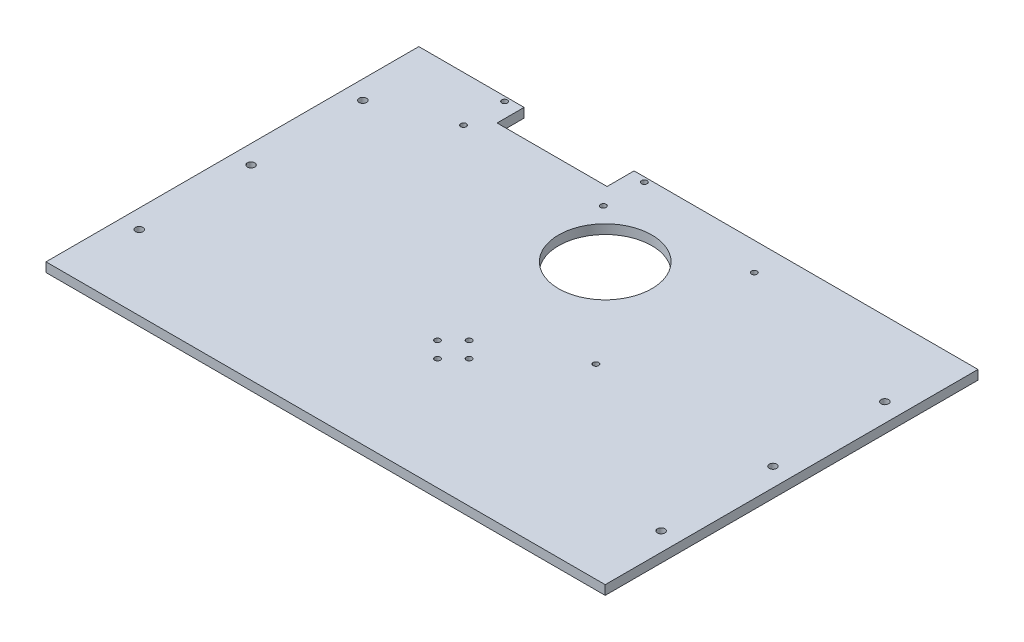
SolidWorks part; units mm, degrees
ref_plane "前视基准面" through (0, 0, 0) normal (0, 0, 1) x (1, 0, 0)
ref_plane "上视基准面" through (0, 0, 0) normal (0, 1, 0) x (1, 0, 0)
ref_plane "右视基准面" through (0, 0, 0) normal (1, 0, 0) x (0, 0, -1)
sketch "Sketch1" plane through (0, 0, 0) normal (0, 1, 0) x (1, 0, 0)
  line L1 (-150, 100) -> (150, 100)
  line L2 (-150, 100) -> (-150, -100)
  line L3 (-150, -100) -> (150, -100)
  line L4 (150, 100) -> (150, -100)
  line L5 (-150, 100) -> (150, -100) construction
  line L6 (-150, -100) -> (150, 100) construction
  point P0 (0, 0)
  dimension "D1" = 200
  dimension "D2" = 300
extrude "Boss-Extrude1" add sketch "Sketch1" along normal blind 5
sketch "Sketch2" plane through (0, 5, 0) normal (0, 1, 0) x (1, 0, 0)
  line L0 (-140, 100) -> (-140, -100) construction
  line L1 (150, 100) -> (-150, 100) construction
  line L2 (-150, -100) -> (150, -100) construction
  line L3 (-150, -90) -> (150, -90) construction
  line L4 (-150, 100) -> (-150, -100) construction
  line L5 (150, -100) -> (150, 100) construction
  line L6 (0, 0) -> (0, 100) construction
  line L7 (0, 0) -> (150, 0) construction
  line L8 (140, 100) -> (140, -100) construction
  circle A0 centre (-140, 0) radius 2
  circle A1 centre (-140, 60) radius 2
  circle A5 centre (-140, -60) radius 2
  circle A7 centre (140, -60) radius 2
  circle A8 centre (140, 60) radius 2
  circle A9 centre (140, 0) radius 2
  circle A13 centre (0, 50) radius 25
  dimension "D3" = 4
  dimension "D4" = 4
  dimension "D5" = 50
  dimension "D8" = 60
  dimension "D1" = 10
  dimension "D2" = 10
extrude "Cut-Extrude2" cut sketch "Sketch2" against normal through all
sketch "Sketch4" plane through (0, 5, 0) normal (0, 1, 0) x (1, 0, 0)
  line L0 (150, 100) -> (-150, 100) construction
  line L1 (-26.5, 97.5) -> (-101.5, 97.5) construction
  line L2 (-26.5, 97.5) -> (-26.5, 75.5) construction
  line L3 (-26.5, 75.5) -> (-101.5, 75.5) construction
  line L4 (-101.5, 97.5) -> (-101.5, 75.5) construction
  line L5 (-26.5, 97.5) -> (-101.5, 75.5) construction
  line L6 (-26.5, 75.5) -> (-101.5, 97.5) construction
  line L7 (-150, 100) -> (-150, -100) construction
  circle A0 centre (-101.5, 97.5) radius 1.5
  circle A1 centre (-26.5, 97.5) radius 1.5
  circle A2 centre (-26.5, 75.5) radius 1.5
  circle A3 centre (-101.5, 75.5) radius 1.5
  point P0 (-64, 86.5)
  dimension "D3" = 3
  dimension "D1" = 75
  dimension "D2" = 22
  dimension "D4" = 2.5
  dimension "D5" = 48.5
extrude "Cut-Extrude3" cut sketch "Sketch4" against normal through all
sketch "Sketch6" plane through (0, 0, 0) normal (0, -1, 0) x (1, 0, 0)
  line L0 (150, -100) -> (-150, -100) construction
  line L1 (-93.5, -100) -> (-34.5, -100)
  line L2 (-93.5, -100) -> (-93.5, -85.5)
  line L3 (-93.5, -85.5) -> (-34.5, -85.5)
  line L4 (-34.5, -100) -> (-34.5, -85.5)
  circle A0 centre (-101.5, -75.5) radius 1.5 construction
  circle A1 centre (-26.5, -75.5) radius 1.5 construction
  dimension "D1" = 8
  dimension "D2" = 8
  dimension "D3" = 10
extrude "Cut-Extrude4" cut sketch "Sketch6" against normal blind 5
sketch "Sketch7" plane through (0, 5, 0) normal (0, 1, 0) x (1, 0, 0)
  line L0 (0, 0) -> (0, -31.5) construction
  line L1 (0, -40) -> (0, -23) construction
  line L2 (-150, -100) -> (150, -100) construction
  circle A0 centre (0, -23) radius 1.5
  circle A1 centre (0, -40) radius 1.5
  circle A2 centre (0, -31.5) radius 8.5 construction
  circle A3 centre (-8.5, -31.5) radius 1.5
  circle A4 centre (8.5, -31.5) radius 1.5
  point P6 (0, -31.5)
  dimension "D2" = 3
  dimension "D4" = 60
  dimension "D3" = 8.5
extrude "Cut-Extrude5" cut sketch "Sketch7" against normal through all
sketch "Sketch8" plane through (0, 5, 0) normal (0, 1, 0) x (1, 0, 0)
  line L0 (45, 100) -> (45, -100) construction
  line L1 (150, 100) -> (-34.5, 100) construction
  line L2 (-150, -100) -> (150, -100) construction
  line L3 (150, -100) -> (150, 100) construction
  circle A0 centre (45, 85) radius 1.5
  circle A1 centre (45, 0) radius 1.5
  dimension "D2" = 3
  dimension "D3" = 3
  dimension "D4" = 15
  dimension "D5" = 85
  dimension "D1" = 105
extrude "Cut-Extrude6" cut sketch "Sketch8" against normal through all
